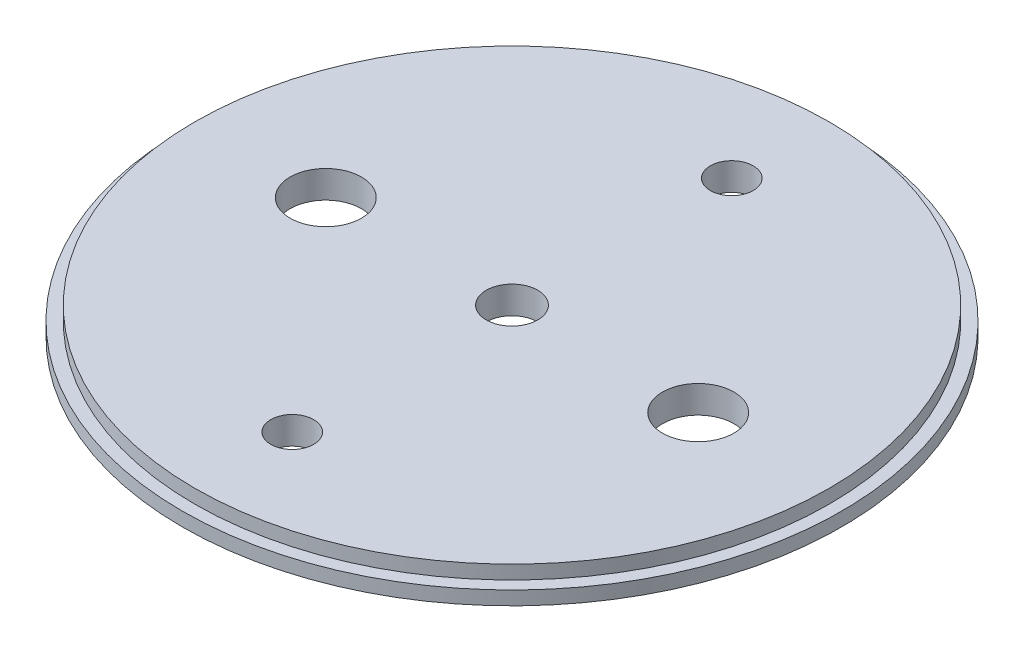
SolidWorks part; units mm, degrees
material "6061-T6 (SS)"
ref_plane "Front Plane" through (0, 0, 0) normal (0, 0, 1) x (1, 0, 0)
ref_plane "Top Plane" through (0, 0, 0) normal (0, 1, 0) x (1, 0, 0)
ref_plane "Right Plane" through (0, 0, 0) normal (1, 0, 0) x (0, 0, -1)
sketch "Sketch1" plane through (0, 0, 0) normal (0, 1, 0) x (1, 0, 0)
  circle A0 centre (0, 0) radius 73.3425
  circle A1 centre (0, 0) radius 76.1746
  dimension "D1" = 146.685
  dimension "D2" = 152.3492
extrude "Boss-Extrude1" add sketch "Sketch1" along normal blind 3.175 contours A0 | A1 A0 region at (0, 0, 0) region at (-74.0201, 0, 0)
extrude "Boss-Extrude2" add sketch "Sketch1<3>" along normal blind 6.35 contours A0 region at (0, 0, 0)
sketch "Sketch1<3>" plane through (0, 0, 0) normal (0, 1, 0) x (1, 0, 0) same geometry as "Sketch1"
sketch "Sketch3" plane through (0, 0, 0) normal (0, -1, 0) x (1, 0, 0)
  line L0 (43.0382, 0) -> (-43.0382, 0) construction
  line L1 (0, -50.8) -> (0, 50.8) construction
  circle A0 centre (0, 0) radius 5.9531
  circle A1 centre (-43.0382, 0) radius 8.25
  circle A2 centre (43.0382, 0) radius 8.25
  circle A3 centre (0, 50.8) radius 4.9609
  circle A4 centre (0, -50.8) radius 4.9609
  point P6 (0, 0)
  point P14 (0, 0)
  dimension "D1" = 11.9062
  dimension "D2" = 16.5001
  dimension "D3" = 9.9219
  dimension "D4" = 101.6
extrude "Cut-Extrude1" cut sketch "Sketch3" against normal through all
sketch "Sketch5" plane through (0, 6.35, 0) normal (0, 1, 0) x (1, 0, 0)
  line L1 (4.0344, 59.0298) -> (-5.11, 58.4088)
  line L2 (-5.11, 58.4088) -> (-9.1444, 50.179)
  line L3 (-9.1444, 50.179) -> (-4.0344, 42.5702)
  line L4 (-4.0344, 42.5702) -> (5.11, 43.1912)
  line L5 (5.11, 43.1912) -> (9.1444, 51.421)
  line L6 (9.1444, 51.421) -> (4.0344, 59.0298)
  line L7 (6.892, -56.8419) -> (8.6785, -47.8523)
  line L8 (8.6785, -47.8523) -> (1.7864, -41.8103)
  line L9 (1.7864, -41.8103) -> (-6.892, -44.7581)
  line L10 (-6.892, -44.7581) -> (-8.6785, -53.7477)
  line L11 (-8.6785, -53.7477) -> (-1.7864, -59.7897)
  line L12 (-1.7864, -59.7897) -> (6.892, -56.8419)
  circle A0 centre (0, 50.8) radius 7.9375 construction
  circle A1 centre (0, -50.8) radius 7.9375 construction
  dimension "D1" = 15.875
